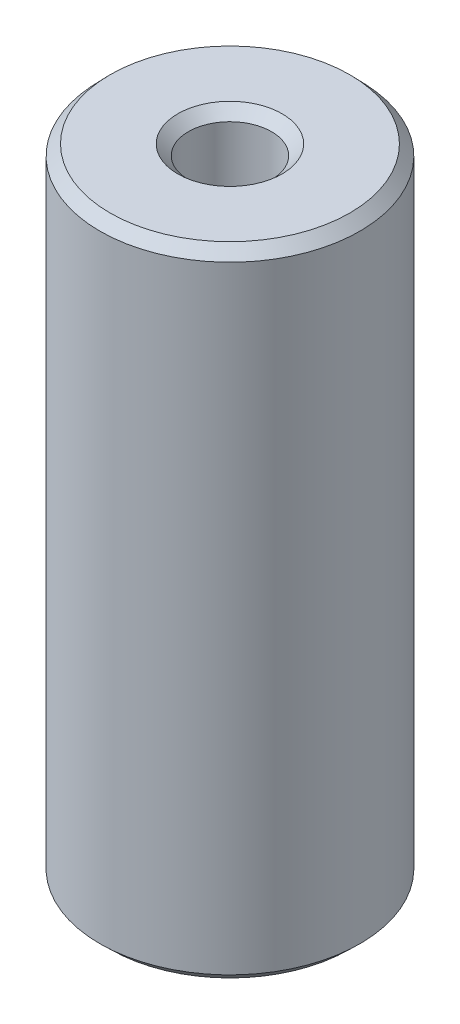
SolidWorks part; units mm, degrees
ref_plane "Front Plane" through (0, 0, 0) normal (0, 0, 1) x (1, 0, 0)
ref_plane "Top Plane" through (0, 0, 0) normal (0, 1, 0) x (1, 0, 0)
ref_plane "Right Plane" through (0, 0, 0) normal (1, 0, 0) x (0, 0, -1)
sketch "Sketch1" plane through (0, 0, 0) normal (0, 1, 0) x (1, 0, 0)
  circle A0 centre (0, 0) radius 5
  dimension "SLEEVE_OD" = 10
extrude "Boss-Extrude1" add sketch "Sketch1" along normal blind 24.5314
sketch "Sketch2" plane through (0, 0, 0) normal (0, 1, 0) x (1, 0, 0)
  circle A0 centre (0, 0) radius 1.598
  dimension "BORE_D" = 3.1961
extrude "Cut-Extrude1" cut sketch "Sketch2" along normal through all
chamfer "Chamfer1" distance 0.4077 angle 43.843 4 edges at (0, 24.5314, 1.598) (0, 0, 1.598) (0, 0, 5) (0, 24.5314, 5) first distance on face at (0, 24.5314, 1.598) first distance on face at (0, 0, 1.598) first distance on face at (0, 24.5314, 5)
